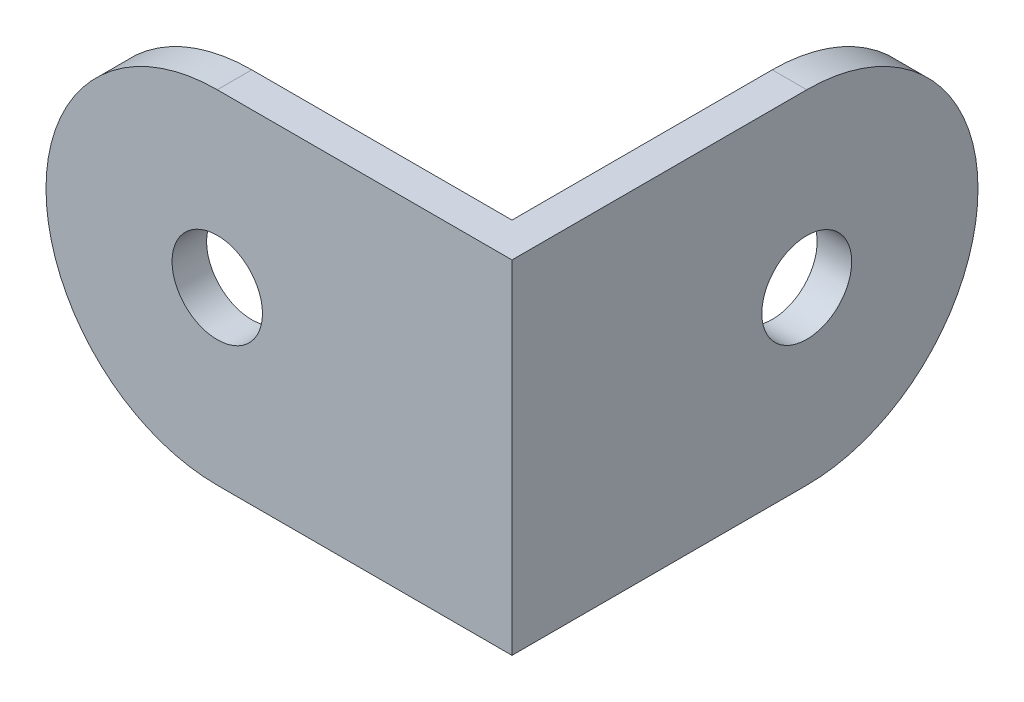
SolidWorks part; units mm, degrees
ref_plane "Front Plane" through (0, 0, 0) normal (0, 0, 1) x (1, 0, 0)
ref_plane "Top Plane" through (0, 0, 0) normal (0, 1, 0) x (1, 0, 0)
ref_plane "Right Plane" through (0, 0, 0) normal (1, 0, 0) x (0, 0, -1)
sketch "Sketch1" plane through (0, 0, 0) normal (0, 1, 0) x (1, 0, 0)
  line L0 (0, 20) -> (0, 0)
  line L1 (0, 0) -> (-20, 0)
  dimension "D1" = 20
  dimension "D2" = 20
extrude "Extrude-Thin1" add sketch "Sketch1" along normal blind 15.875 thin thin type one direction reverse wall 1.6
fillet "Fillet1" 2 edges at (0.8, 15.875, -20) (0.8, 0, -20) type full round first side face at (-6.1333, 15.875, -6.1333) second side face at (-6.1333, 0, -6.1333) middle face at (0.8, 7.9375, -20)
fillet "Fillet2" 2 edges at (-20, 0, 0.8) (-20, 15.875, 0.8) type full round first side face at (-6.1333, 0, -3.4875) second side face at (-6.1333, 15.875, -3.4875) middle face at (-20, 7.9375, 0.8)
sketch "Sketch2" plane through (0, 0, 0) normal (-1, 0, 0) x (0, 0, 1)
  circle A0 centre (-12.0625, 7.9375) radius 2.0825
  arc A1 (-12.0625, 15.875) -> (-12.0625, 0) centre (-12.0625, 7.9375) ccw construction
  dimension "D1" = 4.165
extrude "Cut-Extrude1" cut sketch "Sketch2" against normal blind 10
sketch "Sketch3" plane through (0, 0, 0) normal (0, 0, -1) x (-1, 0, 0)
  circle A0 centre (12.0625, 7.9375) radius 2.0955
  dimension "D1" = 4.191
extrude "Cut-Extrude2" cut sketch "Sketch3" against normal blind 10
